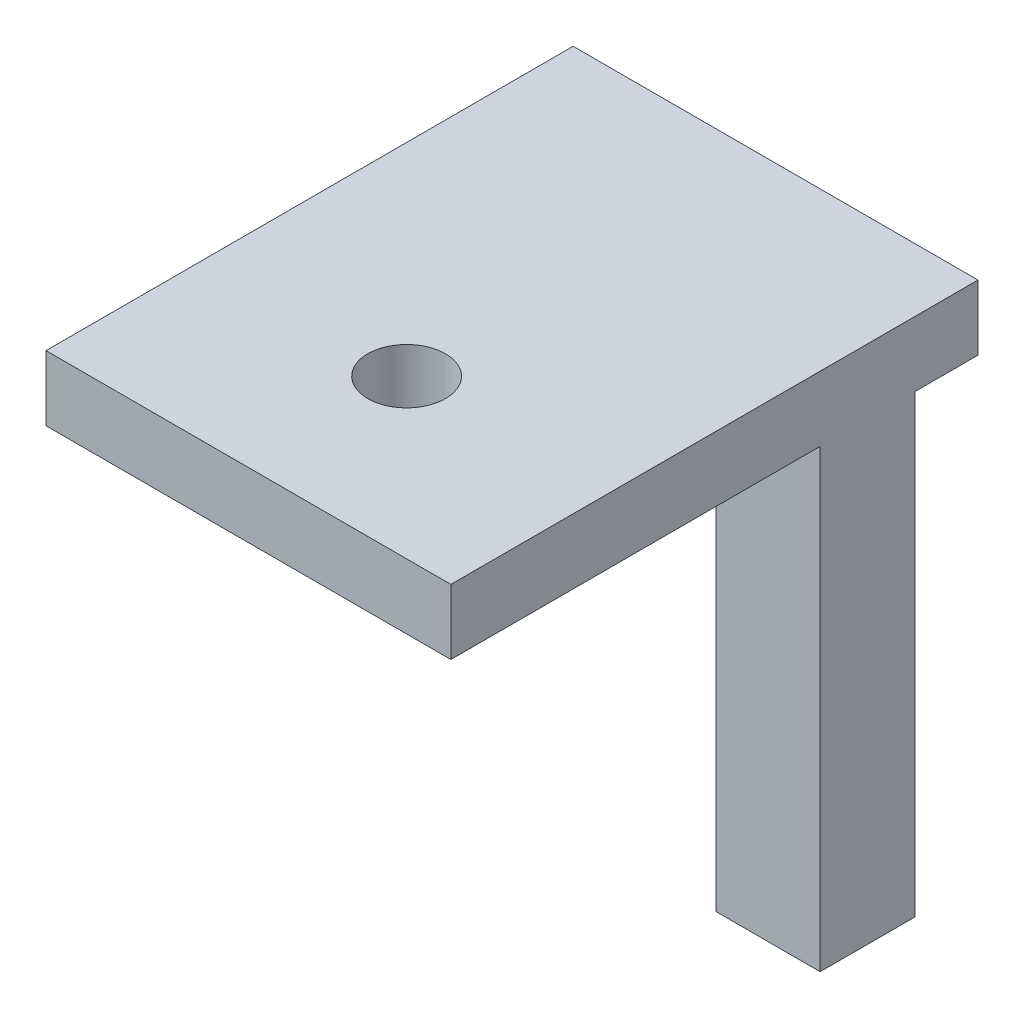
SolidWorks part; units mm, degrees
ref_plane "Front Plane" through (0, 0, 0) normal (0, 0, 1) x (1, 0, 0)
ref_plane "Top Plane" through (0, 0, 0) normal (0, 1, 0) x (1, 0, 0)
ref_plane "Right Plane" through (0, 0, 0) normal (1, 0, 0) x (0, 0, -1)
sketch "Sketch1" plane through (0, 0, 0) normal (0, 1, 0) x (1, 0, 0)
  line L1 (-31.1, 40.4921) -> (31.1, 40.4921)
  line L2 (-31.1, 40.4921) -> (-31.1, -40.4921)
  line L3 (-31.1, -40.4921) -> (31.1, -40.4921)
  line L4 (31.1, 40.4921) -> (31.1, -40.4921)
  line L5 (-31.1, 40.4921) -> (31.1, -40.4921) construction
  line L6 (-31.1, -40.4921) -> (31.1, 40.4921) construction
  point P0 (0, 0)
  dimension "D1" = 62.2
  dimension "D2" = 80.9841
extrude "Boss-Extrude1" add sketch "Sketch1" along normal blind 10
sketch "Sketch2" plane through (0, 10, 0) normal (0, 1, 0) x (1, 0, 0)
  line L0 (-31.1, -40.4921) -> (31.1, -40.4921) construction
  circle A0 centre (0, -16.1921) radius 5.969
  dimension "D1" = 24.3
extrude "Cut-Extrude1" cut sketch "Sketch2" against normal blind 10
sketch "Sketch3" plane through (0, 0, 0) normal (0, -1, 0) x (1, 0, 0)
  line L0 (31.1, -40.4921) -> (-31.1, -40.4921) construction
  line L1 (31.1, -30.7921) -> (15.1, -30.7921)
  line L2 (31.1, -30.7921) -> (31.1, -16.2394)
  line L3 (31.1, -16.2394) -> (15.1, -16.2394)
  line L4 (15.1, -30.7921) -> (15.1, -16.2394)
  dimension "D1" = 16
  dimension "D2" = 9.7
  dimension "D3" = 14.5526
extrude "Boss-Extrude2" add sketch "Sketch3" along normal blind 69.9
